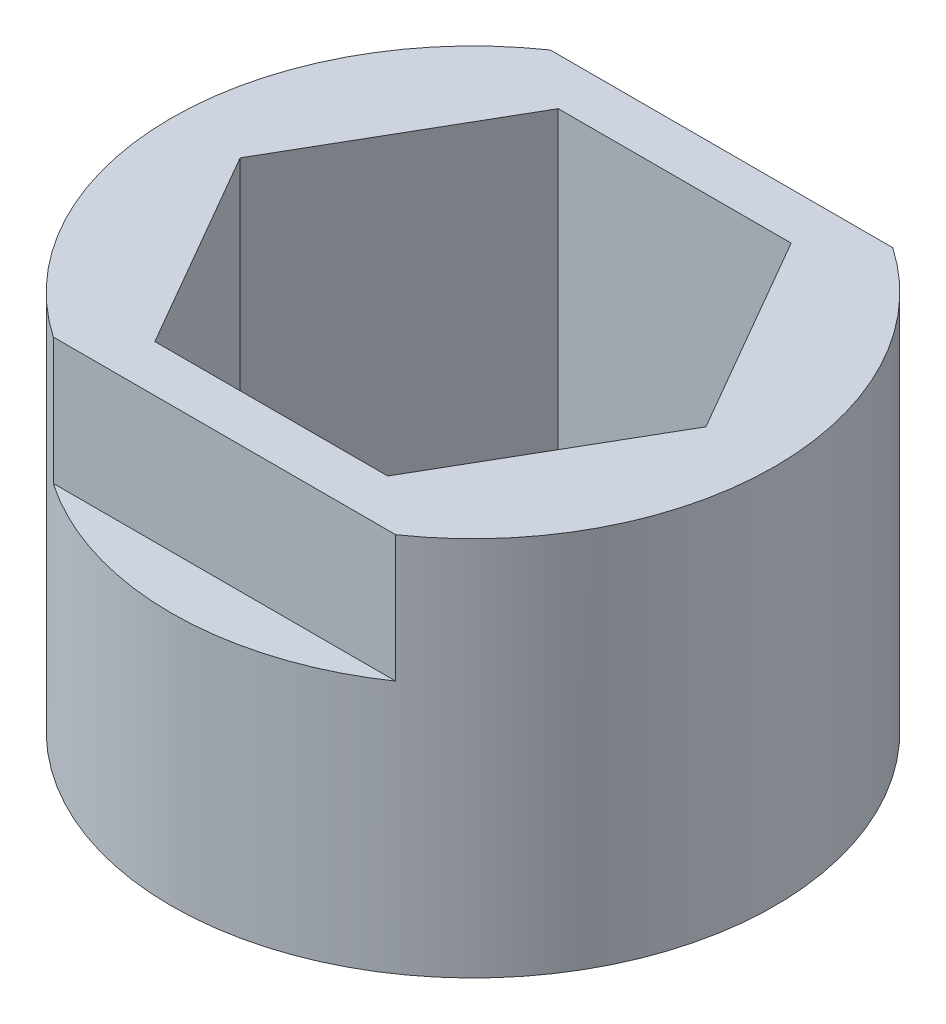
SolidWorks part; units mm, degrees
material "Polyester Resin"
ref_plane "Front Plane" through (0, 0, 0) normal (0, 0, 1) x (1, 0, 0)
ref_plane "Top Plane" through (0, 0, 0) normal (0, 1, 0) x (1, 0, 0)
ref_plane "Right Plane" through (0, 0, 0) normal (1, 0, 0) x (0, 0, -1)
sketch "Sketch1" plane through (0, 0, 0) normal (0, 1, 0) x (1, 0, 0)
  line L1 (-2.9156, 5.05) -> (-5.8312, 0)
  line L2 (-5.8312, 0) -> (-2.9156, -5.05)
  line L3 (-2.9156, -5.05) -> (2.9156, -5.05)
  line L4 (2.9156, -5.05) -> (5.8312, 0)
  line L5 (5.8312, 0) -> (2.9156, 5.05)
  line L6 (2.9156, 5.05) -> (-2.9156, 5.05)
  circle A0 centre (0, 0) radius 5.05 construction
  circle A1 centre (0, 0) radius 7.5565
  dimension "D2" = 15.113
  dimension "D1" = 10.1
extrude "Boss-Extrude1" add sketch "Sketch1" along normal blind 8.89
sketch "Sketch2" plane through (0, 0, 0) normal (0, -1, 0) x (1, 0, 0)
  circle A0 centre (0, 0) radius 7.5565
  circle A1 centre (0, 0) radius 3.3
  dimension "D1" = 6.6
extrude "Boss-Extrude2" add sketch "Sketch2" along normal blind 0.635
sketch "Sketch3" plane through (0, 0, 0) normal (1, 0, 0) x (0, 0, -1)
  line L0 (-6.223, 9.525) -> (-6.223, 5.715)
  line L1 (6.223, 9.525) -> (6.223, 5.715)
  line L2 (-7.5565, -0.635) -> (7.5565, -0.635) construction
  line L3 (-6.223, 9.525) -> (-8.202, 9.525)
  line L4 (-8.202, 9.525) -> (-8.202, 5.715)
  line L5 (-8.202, 5.715) -> (-6.223, 5.715)
  line L6 (6.223, 9.525) -> (8.4791, 9.525)
  line L7 (8.4791, 9.525) -> (8.4791, 5.715)
  line L8 (8.4791, 5.715) -> (6.223, 5.715)
  dimension "D1" = 12.446
  dimension "D2" = 6.223
  dimension "D3" = 3.81
  dimension "D4" = 3.81
  dimension "D5" = 6.35
  dimension "D6" = 6.35
extrude "Cut-Extrude1" cut sketch "Sketch3" against normal through all and the other way through all
equation "\"AB_Central_Bushing_Length\"= .4724in"
equation "\"Solid_Length\"= .025in"
equation "\"Hex_Length\"= 0.35"
equation "\"D1@Boss-Extrude1\"= \"Hex_Length\""
equation "\"D1@Boss-Extrude2\"=\"Solid_Length\""
equation "\"Cutout_Angle\"= 80"
